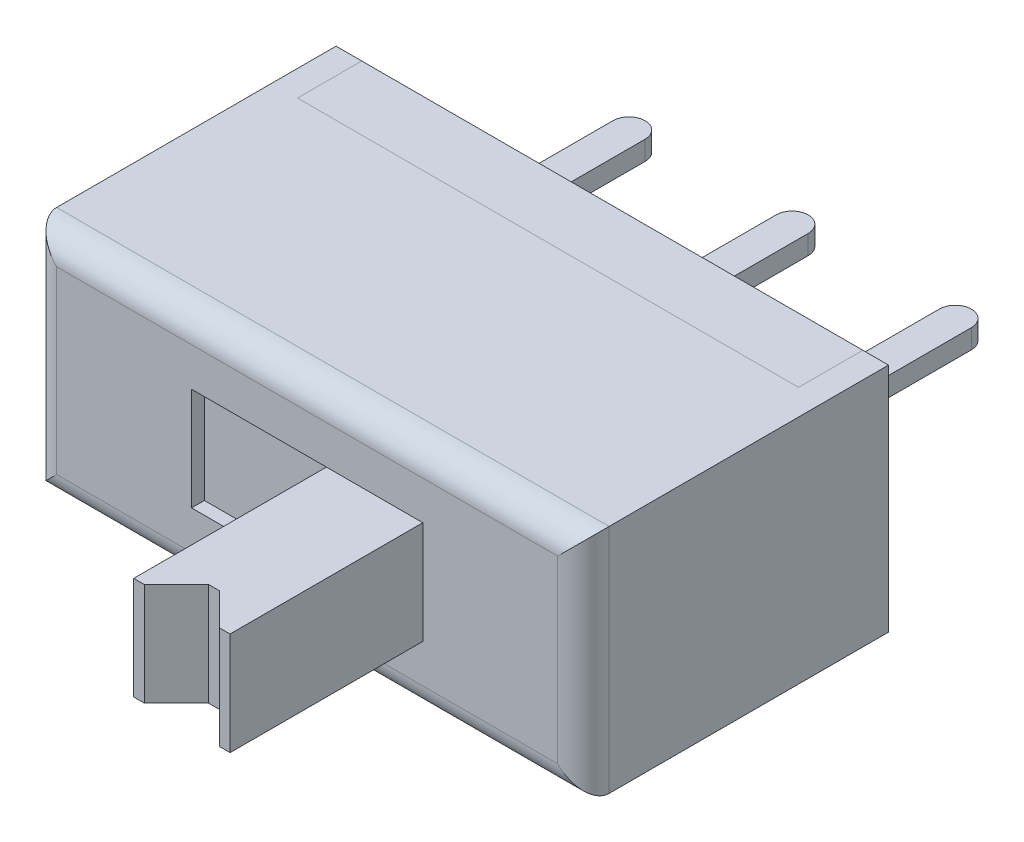
SolidWorks part; units mm, degrees
ref_plane "Front Plane" through (0, 0, 0) normal (0, 0, 1) x (1, 0, 0)
ref_plane "Top Plane" through (0, 0, 0) normal (0, 1, 0) x (1, 0, 0)
ref_plane "Right Plane" through (0, 0, 0) normal (1, 0, 0) x (0, 0, -1)
sketch "Sketch1" plane through (0, 0, 0) normal (0, 0, 1) x (1, 0, 0)
  line L1 (-4.3, 1.8) -> (4.3, 1.8)
  line L2 (-4.3, 1.8) -> (-4.3, -1.8)
  line L3 (-4.3, -1.8) -> (4.3, -1.8)
  line L4 (4.3, 1.8) -> (4.3, -1.8)
  line L5 (-4.3, 1.8) -> (4.3, -1.8) construction
  line L6 (-4.3, -1.8) -> (4.3, 1.8) construction
  point P0 (0, 0)
  dimension "D1" = 8.6
  dimension "D2" = 3.6
extrude "Boss-Extrude1" add sketch "Sketch1" along normal blind 4.75
fillet "Fillet2" radius 0.4 4 edges at (-4.3, 0, 4.75) (0, 1.8, 4.75) (4.3, 0, 4.75) (0, -1.8, 4.75)
sketch "Sketch2" plane through (0, 0, 4.75) normal (0, 0, 1) x (1, 0, 0)
  line L1 (-1.8, 0.8) -> (1.8, 0.8)
  line L2 (-1.8, 0.8) -> (-1.8, -0.8)
  line L3 (-1.8, -0.8) -> (1.8, -0.8)
  line L4 (1.8, 0.8) -> (1.8, -0.8)
  line L5 (-1.8, 0.8) -> (1.8, -0.8) construction
  line L6 (-1.8, -0.8) -> (1.8, 0.8) construction
  point P0 (0, 0)
  dimension "D1" = 1.6
  dimension "D2" = 3.6
extrude "Cut-Extrude1" cut sketch "Sketch2" against normal blind 0.2
sketch "Sketch4" plane through (0, -0.8, 0) normal (0, 1, 0) x (1, 0, 0)
  line L0 (1.8, -4.55) -> (1.8, -7.75)
  line L1 (1.8, -7.75) -> (1.6333, -7.75)
  line L2 (1.6333, -7.75) -> (1.1333, -7.25)
  line L3 (1.1333, -7.25) -> (0.9667, -7.25)
  line L4 (0.9667, -7.25) -> (0.4667, -7.75)
  line L5 (0.4667, -7.75) -> (0.3, -7.75)
  line L6 (0.3, -7.75) -> (0.3, -4.55)
  line L7 (1.8, -4.55) -> (-1.8, -4.55) construction
  line L8 (0.3, -4.55) -> (1.8, -4.55)
  line L9 (3.9, -4.75) -> (-3.9, -4.75) construction
  dimension "D1" = 1.5
  dimension "D2" = 3
  dimension "D3" = 45
  dimension "D4" = 0.5
extrude "Boss-Extrude2" add sketch "Sketch4" along normal up to surface (1.6 mm away) up to face at (0, 0.8, 4.65)
sketch "Sketch8" plane through (0, 0, 0) normal (0, 0, -1) x (-1, 0, 0)
  line L0 (-4.3, 1.8) -> (4.3, 1.8) construction
  line L1 (3.9, -1.8) -> (-3.9, -1.8)
  line L2 (3.9, -1.8) -> (3.9, 1.8)
  line L3 (3.9, 1.8) -> (-3.9, 1.8)
  line L4 (-3.9, -1.8) -> (-3.9, 1.8)
  line L5 (3.9, -1.8) -> (-3.9, 1.8) construction
  line L6 (3.9, 1.8) -> (-3.9, -1.8) construction
  line L7 (-4.3, -1.8) -> (-4.3, 1.8) construction
  point P0 (0, 0)
  dimension "D1" = 0.4
extrude "Cut-Extrude2" cut sketch "Sketch8" against normal blind 1
sketch "Sketch10" plane through (0, 0, 1) normal (0, 0, -1) x (-1, 0, 0)
  line L1 (-0.25, 0.15) -> (0.25, 0.15)
  line L2 (-0.25, 0.15) -> (-0.25, -0.15)
  line L3 (-0.25, -0.15) -> (0.25, -0.15)
  line L4 (0.25, 0.15) -> (0.25, -0.15)
  line L5 (-0.25, 0.15) -> (0.25, -0.15) construction
  line L6 (-0.25, -0.15) -> (0.25, 0.15) construction
  point P0 (0, 0)
  dimension "D1" = 0.5
  dimension "D2" = 0.3
extrude "Boss-Extrude6" add sketch "Sketch10" along normal offset from surface (4.05 mm away) 7.8 up to face at (0.1, 0, 4.75)
fillet "Fillet5" 2 edges at (0.25, 0, -3.05) (-0.25, 0, -3.05) type full round first side face at (0.25, 0, -1.025) second side face at (-0.25, 0, -1.025) middle face at (0, 0, -3.05)
pattern_linear "LPattern3" count 2 spacing 2.54 along (1, 0, 0) count 2 spacing 2.54 along (-1, 0, 0) of "Boss-Extrude6", "Fillet5" pattern seed only yes
sketch "Sketch9" plane through (0, 0, 1) normal (0, 0, -1) x (-1, 0, 0)
  line L1 (-3.9, 1.8) -> (3.9, 1.8)
  line L2 (-3.9, 1.8) -> (-3.9, -1.8)
  line L3 (-3.9, -1.8) -> (3.9, -1.8)
  line L4 (3.9, 1.8) -> (3.9, -1.8)
extrude "Boss-Extrude7" add sketch "Sketch9" along normal blind 1 separate body
